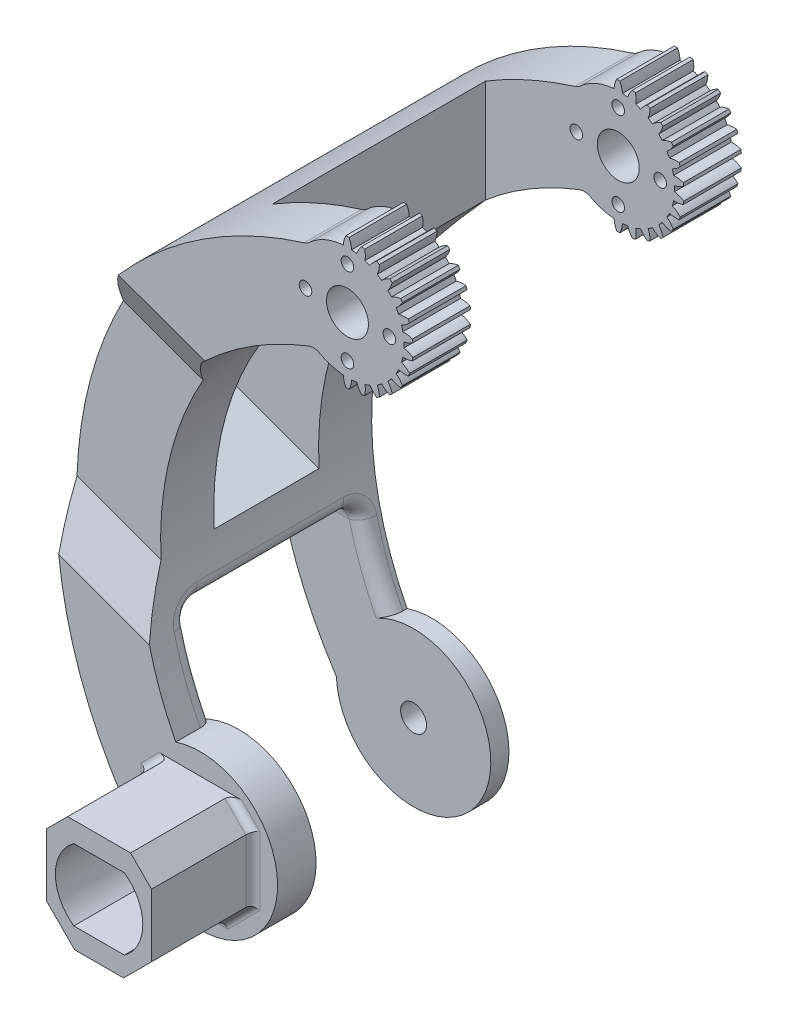
SolidWorks part; units mm, degrees
ref_plane "Alzado" through (0, 0, 0) normal (0, 0, 1) x (1, 0, 0)
ref_plane "Planta" through (0, 0, 0) normal (0, 1, 0) x (1, 0, 0)
ref_plane "Vista lateral" through (0, 0, 0) normal (1, 0, 0) x (0, 0, -1)
sketch "General" plane through (0, 0, 0) normal (0, 0, 1) x (1, 0, 0)
  line L0 (0, -33.4233) -> (0, 47689.0306) construction
  line L1 (6.6907, 0) -> (47729.1446, 0) construction
  line L2 (-11, 14) -> (-11, -14) construction
  line L3 (-23, 14) -> (23, 14) construction
  line L4 (-23, 14) -> (-23, -14) construction
  line L5 (-23, -14) -> (23, -14) construction
  line L6 (23, 14) -> (23, -14) construction
  line L7 (-23, 14) -> (23, -14) construction
  line L8 (-23, -14) -> (23, 14) construction
  line L9 (-53.8528, 23.512) -> (-38.6411, 23.4646) construction
  line L10 (-53.8528, 23.512) -> (-54.1389, 38.7648) construction
  line L11 (-53.8528, 23.512) -> (-42.0695, 24.391) construction
  line L12 (-53.8528, 23.512) -> (-42.0757, 22.5533) construction
  line L13 (-53.8528, 23.512) -> (-42.1693, 21.747) construction
  line L14 (-53.8528, 23.512) -> (-39.8274, 23.7032) construction
  line L15 (-53.8528, 23.512) -> (-39.829, 23.226) construction
  line L16 (0, -50) -> (-37.5362, -81.4966) construction
  line L103 (-42.0757, 22.5533) -> (-40.8989, 22.7984) construction
  line L104 (-39.829, 23.226) -> (-39.8274, 23.7032) construction
  line L105 (-40.8944, 24.138) -> (-42.0695, 24.391) construction
  circle A0 centre (0, -50) radius 30 construction
  circle A1 centre (-53.8528, 23.512) radius 14.0267 construction
  circle A2 centre (-53.8528, 23.512) radius 11.8161 construction
  circle A3 centre (-53.8528, 23.512) radius 12.9735 construction
  circle A4 centre (-11, 0) radius 11 construction
  circle A5 centre (11, 0) radius 11 construction
  circle A6 centre (-37.5362, -81.4966) radius 19 construction
  arc A109 (-42.1693, 21.747) -> (-42.0757, 22.5533) centre (-53.8528, 23.512) ccw construction
  arc A110 (-40.8989, 22.7984) -> (-39.829, 23.226) centre (-41.5742, 26.0406) ccw construction
  arc A111 (-39.8274, 23.7032) -> (-40.8944, 24.138) centre (-41.5916, 20.9005) ccw construction
  arc A112 (-42.0695, 24.391) -> (-42.1576, 25.198) centre (-53.8528, 23.512) ccw construction
  point P30 (0, 0)
  dimension "D1" = 60
  dimension "D8" = 23.6322
  dimension "D9" = 25.947
  dimension "D10" = 28.0535
  dimension "D12" = 22
  dimension "D13" = 38
  dimension "D2" = 50
  dimension "D3" = 28
  dimension "D4" = 12
  dimension "D5" = 46
  dimension "D6" = 12.857
  dimension "D7" = 8.92
  dimension "D11" = 4.445
  dimension "D14" = 130
sketch "dientes left" plane through (0, 0, 0) normal (0, 0, 1) x (1, 0, 0)
  line L0 (0, -33.4233) -> (0, 47689.0306) construction
  line L2 (-52.3069, -19.6337) -> (-41.0879, -19.8625) construction
  line L9 (-53.8528, 23.512) -> (-38.6411, 23.4646) construction
  line L10 (35.2249, 36.7395) -> (32.3069, 26.491) construction
  line L11 (-53.8528, 23.512) -> (-42.0695, 24.391) construction
  line L12 (-53.8528, 23.512) -> (-42.0757, 22.5533) construction
  line L13 (-53.8528, 23.512) -> (-42.1693, 21.747) construction
  line L14 (-53.8528, 23.512) -> (-39.8274, 23.7032) construction
  line L15 (-53.8528, 23.512) -> (-39.829, 23.226) construction
  line L16 (-41.9402, -19.1329) -> (-42.8803, -18.9305) construction
  line L17 (-52.3069, -19.6337) -> (-52.5358, -7.4315) construction
  line L18 (-52.3069, -19.6337) -> (-42.8803, -18.9305) construction
  line L19 (-52.3069, -19.6337) -> (-41.0866, -19.4807) construction
  line L20 (-42.8852, -20.4007) -> (-41.9438, -20.2046) construction
  line L21 (-52.3069, -19.6337) -> (-40.1376, -19.6716) construction
  line L22 (-41.0879, -19.8625) -> (-41.0866, -19.4807) construction
  line L23 (-52.3069, -19.6337) -> (-42.9601, -21.0457) construction
  line L24 (-52.3069, -19.6337) -> (-42.8852, -20.4007) construction
  line L25 (-11, -8.8667) -> (-2.0089, -5.5942) construction
  line L26 (-11, -9.4049) -> (-11, 18009.3981) construction
  line L28 (-11, 0) -> (-11, 9.5) construction
  line L29 (-18.0819, -8.8667) -> (0, -8.8667) construction
  line L33 (-11, -8.8667) -> (-22.1792, -4.7978) construction
  line L35 (-11, 0) -> (-13.8497, -7.8295) construction
  line L103 (-42.0757, 22.5533) -> (-40.8989, 22.7984) construction
  line L104 (-39.829, 23.226) -> (-39.8274, 23.7032) construction
  line L105 (-40.8944, 24.138) -> (-42.0695, 24.391) construction
  line L106 (32.3069, 26.491) -> (37.8505, 37.0466) construction
  line L107 (32.3069, 26.491) -> (37.6564, 34.9915) construction
  line L108 (37.6564, 34.9915) -> (37.934, 35.9748) construction
  line L109 (37.8505, 37.0466) -> (38.032, 36.9492) construction
  line L110 (32.3069, 26.491) -> (42.3228, 27.2382) construction
  line L111 (32.3069, 26.491) -> (32.0638, 39.4559) construction
  line L112 (32.3069, 26.491) -> (42.2379, 24.9907) construction
  line L113 (36.9768, 35.383) -> (37.6564, 34.9915) construction
  line L114 (32.3069, 26.491) -> (38.032, 36.9492) construction
  line L115 (-11, 14) -> (-11, -14) construction
  line L203 (44.4544, -13.8813) -> (52.8267, -14.5629) construction
  line L204 (44.4544, -13.8813) -> (54.4523, -14.0853) construction
  line L205 (44.4544, -13.8813) -> (54.4535, -13.752) construction
  line L206 (54.4523, -14.0853) -> (54.4535, -13.752) construction
  line L207 (44.4544, -13.8813) -> (59.666, -13.9381) construction
  line L208 (52.8267, -14.5629) -> (53.74, -14.3982) construction
  line L209 (44.4544, -13.8813) -> (52.8311, -13.2564) construction
  line L210 (44.4544, -13.8813) -> (52.7601, -15.1365) construction
  line L211 (53.7435, -13.4326) -> (52.8311, -13.2564) construction
  line L212 (-11, 0) -> (-8.1503, -7.8295) construction
  line L213 (-11.4974, -8.6856) -> (-10.5026, -8.6856) construction
  circle A1 centre (-53.8528, 23.512) radius 14.0267 construction
  circle A2 centre (-53.8528, 23.512) radius 11.8161 construction
  circle A3 centre (-53.8528, 23.512) radius 12.9735 construction
  arc A7 (-41.0866, -19.4807) -> (-41.9402, -19.1329) centre (-42.498, -21.7229) ccw construction
  circle A8 centre (-52.3069, -19.6337) radius 11.2214 construction
  arc A9 (-42.8803, -18.9305) -> (-42.9508, -18.2849) centre (-52.3069, -19.6337) ccw construction
  circle A10 centre (-52.3069, -19.6337) radius 10.3788 construction
  arc A11 (-42.9601, -21.0457) -> (-42.8852, -20.4007) centre (-52.3069, -19.6337) ccw construction
  arc A12 (-41.9438, -20.2046) -> (-41.0879, -19.8625) centre (-42.484, -17.6108) ccw construction
  circle A13 centre (-52.3069, -19.6337) radius 9.4529 construction
  circle A17 centre (-11, 0) radius 8.8667 construction
  arc A20 (-11.598, -8.0528) -> (-10.402, -8.0528) centre (-11, 0) ccw
  circle A47 centre (32.3069, 26.491) radius 11.0275 construction
  arc A48 (37.934, 35.9748) -> (38.032, 36.9492) centre (35.2249, 36.7395) ccw construction
  circle A49 centre (32.3069, 26.491) radius 11.9227 construction
  circle A50 centre (32.3069, 26.491) radius 10.0437 construction
  circle A80 centre (44.4544, -13.8813) radius 9.3 construction
  arc A81 (53.74, -14.3982) -> (54.4523, -14.0853) centre (52.7733, -11.2306) ccw construction
  arc A82 (52.7601, -15.1365) -> (52.8267, -14.5629) centre (41.0597, -13.4871) ccw construction
  circle A83 centre (44.4544, -13.8813) radius 8.4 construction
  arc A84 (52.8311, -13.2564) -> (52.7429, -12.4495) centre (41.0478, -14.1355) ccw construction
  circle A85 centre (44.4544, -13.8813) radius 10 construction
  arc A86 (54.4535, -13.752) -> (53.7435, -13.4326) centre (52.7493, -16.5916) ccw construction
  arc A87 (-11.598, -8.0528) -> (-11.2265, -9.4022) centre (-8.1503, -7.8295) ccw
  arc A109 (-42.1693, 21.747) -> (-42.0757, 22.5533) centre (-53.8528, 23.512) ccw construction
  arc A110 (-40.8989, 22.7984) -> (-39.829, 23.226) centre (-41.5742, 26.0406) ccw construction
  arc A111 (-39.8274, 23.7032) -> (-40.8944, 24.138) centre (-41.5916, 20.9005) ccw construction
  arc A112 (-42.0695, 24.391) -> (-42.1576, 25.198) centre (-53.8528, 23.512) ccw construction
  arc A117 (-10.402, -8.0528) -> (-11.598, -8.0528) centre (-11, 0) ccw
  arc A119 (-10.7735, -9.4022) -> (-10.402, -8.0528) centre (-13.8497, -7.8295) ccw
  circle A124 centre (-11, 0.0951) radius 9.5
  point P54 (32.3206, 26.4908)
  point P195 (-10.9863, -0.0002)
  point P220 (-11, 0)
  dimension "D8" = 23.6322
  dimension "D9" = 25.947
  dimension "D10" = 28.0535
  dimension "D19" = 16.8
  dimension "D20" = 18.6
  dimension "D21" = 20
  dimension "D3" = 16.15
  dimension "D4" = 17.7333
  dimension "D28" = 19
  dimension "D6" = 12.857
  dimension "D7" = 8.92
  dimension "D11" = 4.445
  dimension "D12" = 0.99
  dimension "D13" = 4.475
  dimension "D14" = 11.815
  dimension "D15" = 10.6558
  dimension "D17" = 12.86
  dimension "D18" = 8.92
  dimension "D22" = 4.48
  dimension "a" = 20
  dimension "D5" = 0.9948
  dimension "D16" = 20
sketch "Cilindro" plane through (0, 0, 0) normal (0, 0, 1) x (1, 0, 0)
  circle A0 centre (-11, 0) radius 8.075
  dimension "D1" = 16.15
extrude "Saliente-Extruir2" add sketch "Cilindro" along normal mid plane 47
extrude "Saliente-Extruir3" add sketch "dientes left" along normal through all and the other way through all contours A20 A87 region at (-11, -8.6467, 0)
pattern_circular "CirPattern2" count 14 every 13.846 about axis through (-11, 0, 23.5) along (0, 0, 1) of "Saliente-Extruir3"
sketch "Croquis5" plane through (0, 0, 0) normal (0, 0, 1) x (1, 0, 0)
  line L0 (-11, 14) -> (-11, -14) construction
  line L1 (-16.7525, 5.6669) -> (-11, -5.1975)
  arc A0 (-11, -5.1975) -> (-41.0638, -71.0244) centre (0, -50) ccw
  arc A1 (-16.7525, 5.6669) -> (-48.578, -81.9317) centre (0, -50) ccw
  circle A2 centre (-37.5362, -81.4966) radius 11.0504 construction
  circle A3 centre (-37.5362, -81.4966) radius 1.8517
  arc A4 (-48.578, -81.9317) -> (-41.0638, -71.0244) centre (-37.5362, -81.4966) ccw
  dimension "D1" = 12
extrude "Saliente-Extruir4" add sketch "Croquis5" along normal up to surface and the other way up to surface up to face at (-5.9921, 0, 23.5) other way up to face at (-5.9921, 0, -23.5)
sketch "Croquis10" plane through (0, 0, 23.5) normal (0, 0, 1) x (1, 0, 0)
  circle A0 centre (-11, 0) radius 3
  dimension "D1" = 6
extrude "Cortar-Extruir5" cut sketch "Croquis10" against normal through all and the other way blind 10
fillet "Fillet1" radius 2 2 edges at (-15.6492, -6.6023, 0) (-16.7525, 5.6669, 0)
sketch "Croquis11" plane through (0, 0, 23.5) normal (0, 0, 1) x (1, 0, 0)
  line L0 (-11, 0) -> (49989, 0) construction
  line L1 (-11, 0) -> (-11, 50000) construction
  circle A0 centre (-17, 0) radius 0.9
  circle A1 centre (-11, 6) radius 0.9
  circle A2 centre (-5, 0) radius 0.9
  circle A3 centre (-11, -6) radius 0.9
  point P16 (-11, 0)
  dimension "D2" = 1.8
  dimension "D1" = 6
  dimension "D4" = 0
  dimension "D5" = 0
  dimension "D3" = 4
extrude "Cortar-Extruir6" cut sketch "Croquis11" against normal through all
sketch "Croquis6" plane through (0, 0, 0) normal (0, 1, 0) x (1, 0, 0)
  line L1 (-30, -15.25) -> (30, -15.25)
  line L2 (-30, -15.25) -> (-30, 15.25)
  line L3 (-30, 15.25) -> (30, 15.25)
  line L4 (30, -15.25) -> (30, 15.25)
  line L5 (-30, -15.25) -> (30, 15.25) construction
  line L6 (-30, 15.25) -> (30, -15.25) construction
  point P0 (0, 0)
  dimension "D1" = 60
  dimension "D2" = 30.5
extrude "Cortar-Extruir1" cut sketch "Croquis6" against normal up to next and the other way up to next
sketch "Croquis7" plane through (0, 0, 0) normal (1, 0, 0) x (0, 0, -1)
  line L0 (0, -62.4966) -> (0, -100.4966) construction
  line L1 (-12.5, -103.4966) -> (12.5, -103.4966)
  line L2 (-12.5, -103.4966) -> (-12.5, -59.4966)
  line L3 (-12.5, -59.4966) -> (12.5, -59.4966)
  line L4 (12.5, -103.4966) -> (12.5, -59.4966)
  line L5 (-12.5, -103.4966) -> (12.5, -59.4966) construction
  line L6 (-12.5, -59.4966) -> (12.5, -103.4966) construction
  point P0 (0, -81.4966)
  dimension "D1" = 25
  dimension "D2" = 44
extrude "Cortar-Extruir2" cut sketch "Croquis7" against normal through all both
ref_plane "Plano1" through (-17.2969, 6.3042, 0) normal (-0.9395, 0.3424, 0) x (0, 0, 1)
sketch "Croquis8" plane through (-17.2969, 6.3042, 0) normal (-0.9395, 0.3424, 0) x (0, 0, 1)
  line L0 (23.5, -26.0212) -> (15.1, -39.1889)
  line L1 (23.5, -93.613) -> (23.5, -0.6948) construction
  line L2 (15.1, -39.1889) -> (15.1, -65)
  line L3 (15.1, -65) -> (18.0068, -72.5389)
  line L4 (18.0068, -72.5389) -> (23.5, -72.5389)
  line L5 (23.5, -72.5389) -> (23.5, -26.0212)
  line L6 (0, 0) -> (0, -50000) construction
  line L7 (-15.1, -93.613) -> (-15.1, -100.4735)
  line L8 (-23.5, -72.5389) -> (-23.5, -26.0212)
  line L11 (-15.1, -39.1889) -> (-15.1, -65)
  line L12 (-23.5, -26.0212) -> (-15.1, -39.1889)
  line L13 (-23.5, -100.4735) -> (-12.5, -100.4735) construction
  line L14 (-15.1, -65) -> (-15.1, -93.613)
  line L15 (-12.5, -93.613) -> (-23.5, -93.613) construction
  line L16 (-15.1, -100.4735) -> (-23.5, -100.4735)
  line L17 (-23.5, -100.4735) -> (-23.5, -72.5389)
  line L18 (23.5, -93.613) -> (23.5, -0.6948) construction
  line L19 (-7.5, -35) -> (7.5, -35)
  line L20 (-7.5, -35) -> (-7.5, -65)
  line L21 (-7.5, -65) -> (7.5, -65)
  line L22 (7.5, -35) -> (7.5, -65)
  line L23 (-7.5, -35) -> (7.5, -65) construction
  line L24 (-7.5, -65) -> (7.5, -35) construction
  line L25 (-12.5, -75.5389) -> (12.5, -75.5389) construction
  point P13 (0, -50)
  dimension "D1" = 50
  dimension "D2" = 30
  dimension "D3" = 15
  dimension "D4" = 8.4
  dimension "D5" = 3
extrude "Cortar-Extruir3" cut sketch "Croquis8" along normal through all both and the other way through all
sketch "Croquis9" plane through (0, 0, 23.5) normal (0, 0, 1) x (1, 0, 0)
  circle A0 centre (-37.5362, -81.4966) radius 11.2842
  circle A1 centre (-37.5362, -81.4966) radius 46.3237
  circle M1 centre (-37.5362, -81.4966) radius 1.8517
  arc M2 (-41.0638, -71.0244) -> (-44.8352, -60.8656) centre (0, -50) cw
  line M3 (-44.8352, -60.8656) -> (-57.8082, -56.1373)
  arc M4 (-57.8082, -56.1373) -> (-48.578, -81.9317) centre (0, -50) ccw
  arc M8 (-48.578, -81.9317) -> (-41.0638, -71.0244) centre (-37.5362, -81.4966) ccw
extrude "Cortar-Extruir4" cut sketch "Croquis9" against normal up to vertex (5.4932 mm away) contours A0 M2 M3 M4 | A0 M2 M4 M8 M1 region at (-41.3975, -71.0616, 23.5) region at (-49.9374, -67.068, 23.5) up to point (-57.8082, -56.1373, 18.0068)
sketch "Sketch1" plane through (0, 0, 0) normal (0, 0, 1) x (1, 0, 0)
  line L1 (-45.0362, -73.4966) -> (-30.0362, -73.4966)
  line L2 (-45.0362, -73.4966) -> (-45.0362, -89.4966)
  line L3 (-45.0362, -89.4966) -> (-30.0362, -89.4966)
  line L4 (-30.0362, -73.4966) -> (-30.0362, -89.4966)
  line L5 (-45.0362, -73.4966) -> (-30.0362, -89.4966) construction
  line L6 (-45.0362, -89.4966) -> (-30.0362, -73.4966) construction
  point P0 (-37.5362, -81.4966)
  dimension "D1" = 15
  dimension "D2" = 16
extrude "Boss-Extrude1" add sketch "Sketch1" along normal blind 20 from surface starting at face at (-35.6844, -81.4966, 12.5)
sketch "Sketch2" plane through (0, 0, 12.5) normal (0, 0, 1) x (1, 0, 0)
  line L1 (-43.8362, -76.3966) -> (-31.2362, -76.3966)
  line L2 (-43.8362, -76.3966) -> (-43.8362, -86.5966)
  line L3 (-43.8362, -86.5966) -> (-31.2362, -86.5966)
  line L4 (-31.2362, -76.3966) -> (-31.2362, -86.5966)
  line L5 (-43.8362, -76.3966) -> (-31.2362, -86.5966) construction
  line L6 (-43.8362, -86.5966) -> (-31.2362, -76.3966) construction
  circle A0 centre (-37.5362, -81.4966) radius 5.1 construction
  dimension "D1" = 10.2
  dimension "D2" = 12.6
  dimension "D3" = 10.2
extrude "Cut-Extrude1" cut sketch "Sketch2" along normal blind 6 from offset 4
sketch "Sketch4" plane through (0, 0, 0) normal (0, 0, -1) x (-1, 0, 0)
  line L1 (31.4362, -76.3966) -> (43.6362, -76.3966)
  line L2 (31.4362, -76.3966) -> (31.4362, -86.5966)
  line L3 (31.4362, -86.5966) -> (43.6362, -86.5966)
  line L4 (43.6362, -76.3966) -> (43.6362, -86.5966)
  line L5 (31.4362, -76.3966) -> (43.6362, -86.5966) construction
  line L6 (31.4362, -86.5966) -> (43.6362, -76.3966) construction
  point P0 (37.5362, -81.4966)
  dimension "D1" = 12.2
  dimension "D2" = 10.2
extrude "Cut-Extrude13" cut sketch "Sketch4" against normal blind 6 from surface starting at face at (-44.3282, -70.9581, 12.5)
sketch "Sketch3" plane through (0, 0, 32.5) normal (0, 0, 1) x (1, 0, 0)
  line L1 (-41.149, -76.3966) -> (-33.9234, -76.3966)
  line L3 (-41.149, -86.5966) -> (-33.9234, -86.5966)
  line L5 (-41.9556, -77.0772) -> (-33.1168, -85.916) construction
  line L6 (-41.9556, -85.916) -> (-33.1168, -77.0772) construction
  arc A0 (-41.149, -76.3966) -> (-41.149, -86.5966) centre (-37.5362, -81.4966) ccw
  arc A1 (-33.9234, -86.5966) -> (-33.9234, -76.3966) centre (-37.5362, -81.4966) ccw
  dimension "D1" = 12.5
  dimension "D2" = 10.2
extrude "Cut-Extrude2" cut sketch "Sketch3" against normal up to next
sketch "Sketch7" plane through (0, 0, 0) normal (0, 1, 0) x (1, 0, 0)
  line L0 (-45.0362, -32.5) -> (-45.0362, -18.0068) construction
  line L1 (-42.0362, -12.5) -> (-32.0362, -12.5)
  line L2 (-42.0362, -12.5) -> (-42.0362, -32.5)
  line L3 (-42.0362, -32.5) -> (-32.0362, -32.5)
  line L4 (-32.0362, -12.5) -> (-32.0362, -32.5)
  line L5 (-42.0362, -12.5) -> (-32.0362, -32.5) construction
  line L6 (-42.0362, -32.5) -> (-32.0362, -12.5) construction
  line L7 (-45.0362, -32.5) -> (-30.0362, -32.5) construction
  point P0 (-37.0362, -22.5)
  dimension "D1" = 10
  dimension "D2" = 20
  dimension "D3" = 3
  dimension "D4" = 0
chamfer "Chamfer1" distance 3 angle 45 2 edges at (-30.0362, -73.4966, 25.2534) (-45.0362, -73.4966, 25.2534)
chamfer "Chamfer2" distance 4 angle 45 2 edges at (-30.0362, -89.4966, 25.2534) (-45.0362, -89.4966, 25.2534)
fillet "Fillet2" radius 1 7 edges at (-45.0362, -80.9966, 18.0068) (-43.0362, -87.4966, 18.0068) (-32.0362, -87.4966, 18.0068) (-37.5362, -89.4966, 18.0068) (-31.5362, -74.9966, 18.0068) (-30.0362, -80.9966, 18.0068) (-43.5362, -74.9966, 18.0068)
sketch "Sketch8" plane through (0, 0, 0) normal (0, 0, 1) x (1, 0, 0)
  circle A1 centre (-17, 0) radius 1.75
  dimension "D1" = 3.5
extrude "Cut-Extrude15" cut sketch "Sketch8" along normal blind 4 from surface starting at face at (-8, 0, -23.5)
pattern_circular "CirPattern3" count 4 over 360 about axis through (-11, 0, -23.5) along (0, 0, 1) of "Cut-Extrude15"
sketch "Sketch9" plane through (0, 0, 0) normal (0, 0, 1) x (1, 0, 0)
  circle A0 centre (-37.5362, -81.4966) radius 3.5
  circle A1 centre (-37.5362, -81.4966) radius 1.8517
  dimension "D1" = 7
extrude "Boss-Extrude2" add sketch "Sketch9" against normal blind 2 from surface contours A0 region at (-40.9372, -81.4966, 0) starting at face at (-37.5362, -79.6449, -15.1)
fillet "Fillet5" radius 2 5 edges at (-51.2486, -59.4966, 12.5) (-43.4881, -65.3963, 12.5) (-43.4881, -65.3963, -12.5) (-45.145, -59.4966, 0) (-51.2486, -59.4966, -12.5)
fillet "Fillet3" radius 2 1 edges at (-37.5362, -77.9966, -15.1)
sketch "Sketch10" plane through (0, 0, 0) normal (0, 0, 1) x (1, 0, 0)
  line L0 (12.5297, 20.3914) -> (-76.621, 20.3914)
  line L1 (12.5297, 20.3914) -> (12.5297, -101.3186)
  line L2 (-76.621, 20.3914) -> (-76.621, -101.3186)
  line L3 (12.5297, -101.3186) -> (-76.621, -101.3186)
equation "\"Z\"= 28"
equation "\"De\"= 19"
equation "\"M\" = \"De\" / ( \"Z\" + 2 )"
equation "\"Dp\"= \"M\" * \"Z\""
equation "\"e\"= \"M\" * 3.1416 / 2"
equation "\"X\" = 0"
equation "\"alpha\"= 20"
equation "\"Din\"= \"Dp\" - ( 2 * \"M\" * 1.25 )"
equation "\"a@dientes left\"=\"alpha\""
equation "\"D3@dientes left\"=\"Din\""
equation "\"D4@dientes left\"=\"Dp\""
equation "\"D5@dientes left\"=\"e\"-\"X\""
equation "\"D16@dientes left\"=\"alpha\""
equation "\"D28@dientes left\"=\"De\""
